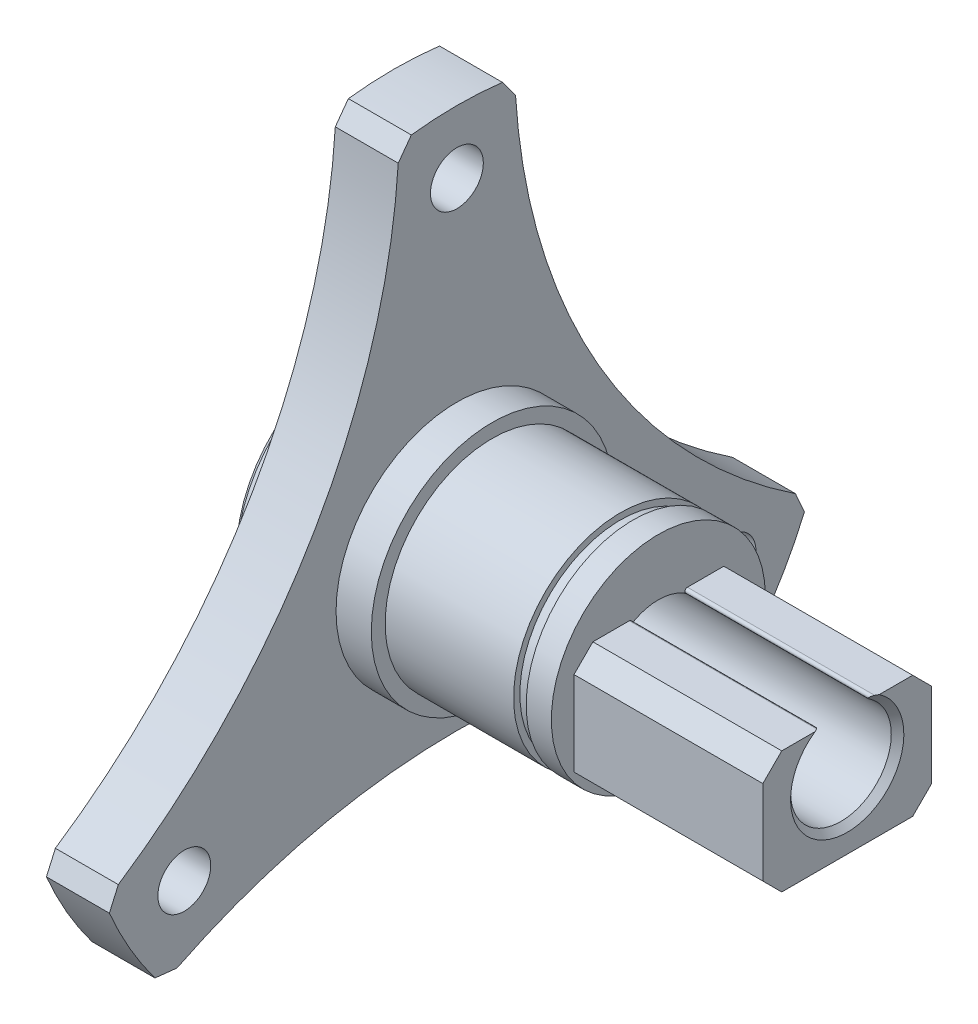
SolidWorks part; units mm, degrees
note: '?' marks a value the reader was unsure of.
material "6061-T6 (SS)"
ref_plane "前视基准面" through (0, 0, 0) normal (0, 0, 1) x (1, 0, 0)
ref_plane "上视基准面" through (0, 0, 0) normal (0, 1, 0) x (1, 0, 0)
ref_plane "右视基准面" through (0, 0, 0) normal (1, 0, 0) x (0, 0, -1)
ref_axis "基准轴1" through (48.51, 0, 0) along (-1, 0, 0)?
sketch "草图1" plane through (0, 0, 0) normal (0, 0, 1) x (1, 0, 0)
  line L0 (0, 0) -> (0, 10)
  line L2 (3, 10) -> (3, 30)
  line L3 (3, 30) -> (8, 30)
  line L4 (8, 30) -> (8, 9.6)
  line L5 (8, 9.6) -> (10.8, 9.6)
  line L6 (10.8, 9.6) -> (10.8, 8.5)
  line L7 (10.8, 8.5) -> (21, 8.5)
  line L12 (21, 8.5) -> (21, 8)
  line L13 (21, 8) -> (22, 8)
  line L14 (22, 8) -> (22, 8.5)
  line L15 (22, 8.5) -> (24, 8.5)
  line L16 (24, 8.5) -> (24, 0)
  line L19 (24, 0) -> (0, 0)
  line L21 (0, 10) -> (3, 10)
  dimension "D1" = 8.5
  dimension "D2" = 9.6
  dimension "D7" = 10.2
  dimension "D8" = 2.8
  dimension "D9" = 5
  dimension "D10" = 30
  dimension "D11" = 10
  dimension "D13" = 3
  dimension "D16" = 8
  dimension "D17" = 1
  dimension "D18" = 8.5
  dimension "D19" = 2
revolve "旋转1" add sketch "草图1" angle 360 about L19
sketch "草图2" plane through (24, 0, 0) normal (1, 0, 0) x (0, 0, -1)
  circle A0 centre (0, 0) radius 4
  dimension "D1" = 8
extrude "切除-拉伸1" cut sketch "草图2" against normal through all
sketch "草图3" plane through (0, 0, 0) normal (-1, 0, 0) x (0, 0, 1)
  circle A0 centre (0, 0) radius 8
  dimension "D1" = 16
extrude "切除-拉伸2" cut sketch "草图3" against normal blind 8
chamfer "倒角1" distance 4 angle 30 1 edges at (8, 0, 4) first distance on face at (8, 0, 8)
sketch "草图5" plane through (3, 0, 0) normal (-1, 0, 0) x (0, 0, 1)
  circle A0 centre (0, 0) radius 25 construction
  circle A1 centre (0, 25) radius 2.5
  circle A2 centre (21.6506, -12.5) radius 2.5
  circle A3 centre (-21.6506, -12.5) radius 2.5
  point P12 (0, 0)
  dimension "D1" = 50
  dimension "D2" = 3
  dimension "D3" = 5
hole_wizard "M5 螺纹孔1" positions "3D草图1" profile "草图6" tap size "M5" standard "GB" end condition through all
sketch3d "3D草图1"
  point P0 (3, 25, 0)
  point P3 (3, -12.5, 21.6506)
  point P6 (3, -12.5, -21.6506)
cosmetic thread "孔螺蚊线1" parameters "D2"=5
cosmetic thread "孔螺蚊线2" parameters "D2"=5
cosmetic thread "孔螺蚊线3" parameters "D2"=5
sketch "草图6" plane through (3, 25, 0) normal (0, 1, 0) x (0, 0, 1)
  line L0 (0, 0) -> (0, 21)
  line L1 (0, 21) -> (2.1, 21)
  line L2 (2.1, 21) -> (2.1, 0)
  line L5 (2.1, 0) -> (0, 0)
  line L11 (0, -6.35) -> (0, 107.95) construction
  dimension "通孔螺纹孔钻头直径" = 4.2
  dimension "通孔螺纹孔钻头深度" = 21
sketch "草图4" plane through (3, 0, 0) normal (-1, 0, 0) x (0, 0, 1)
  line L0 (0, 0) -> (0, -63) construction
  arc A0 (-27.7102, -21.381) -> (27.7102, -21.381) centre (0, 0) ccw
  arc A1 (27.7102, -21.381) -> (-27.7102, -21.381) centre (0, -63) ccw
  dimension "D1" = 70
  dimension "D3" = 100
  dimension "D2" = 63
extrude "切除-拉伸3" cut sketch "草图4" against normal through all
pattern_circular "阵列(圆周)1" count 3 over 360 about axis through (0, 0, 0) along (1, 0, 0) of "切除-拉伸3"
chamfer "倒角2" distance 1 angle 45 6 edges at (5.5, 29.6462, -4.594) (5.5, 29.6462, 4.594) (5.5, -10.8446, 27.9713) (5.5, -18.8016, 23.3773) (5.5, -18.8016, -23.3773) (5.5, -10.8446, -27.9713) first distance on face at (5.5, 29.8231, 0) first distance on face at (5.5, -14.9115, 25.8275) first distance on face at (5.5, -14.9115, -25.8275)
chamfer "倒角4" distance 0.5 angle 45 1 edges at (0, 0, -10)
sketch "草图7" plane through (24, 0, 0) normal (1, 0, 0) x (0, 0, -1)
  line L0 (0, 0) -> (0, 2.7252) construction
  line L1 (-6.7, -6) -> (6.7, -6)
  line L2 (-6.7, -6) -> (-6.7, 3.7081)
  line L3 (-6.7, 3.7081) -> (-1.5, 3.7081)
  line L4 (6.7, -6) -> (6.7, 3.7081)
  line L5 (1.5, 3.7081) -> (6.7, 3.7081)
  arc A0 (-1.5, 3.7081) -> (1.5, 3.7081) centre (0, 0) ccw
  dimension "D1" = 8
  dimension "D2" = 13.4
  dimension "D3" = 6
  dimension "D4" = 3
extrude "凸台-拉伸1" add sketch "草图7" along normal blind 15
chamfer "倒角5" distance 1.5 angle 45 4 edges at (31.5, -6, -6.7) (31.5, -6, 6.7) (31.5, 3.7081, -6.7) (31.5, 3.7081, 6.7)
chamfer "倒角6" distance 0.5 angle 45 1 edges at (39, -4, 0)
fillet "圆角1" radius 0.2 2 edges at (31.25, 3.7081, 1.5) (31.25, 3.7081, -1.5)
